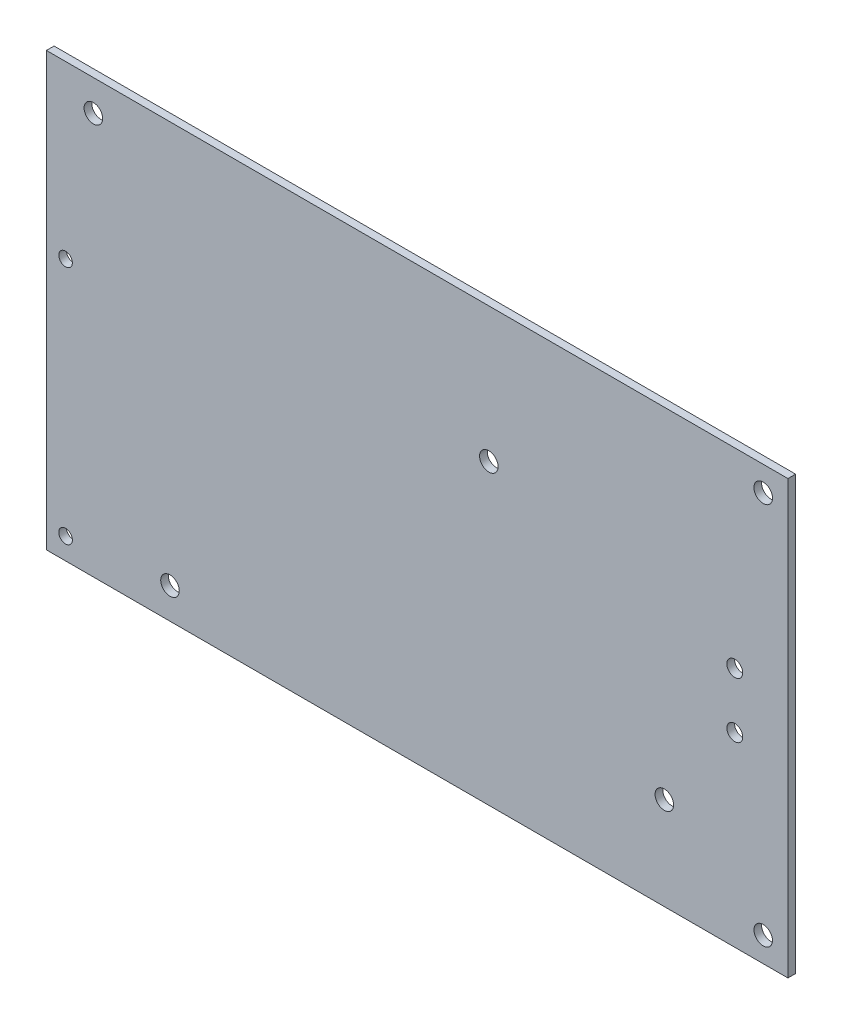
SolidWorks part; units mm, degrees
ref_plane "Front" through (0, 0, 0) normal (0, 0, 1) x (1, 0, 0)
ref_plane "Top" through (0, 0, 0) normal (0, 1, 0) x (1, 0, 0)
ref_plane "Right" through (0, 0, 0) normal (1, 0, 0) x (0, 0, -1)
sketch "Sketch1" plane through (0, 0, 0) normal (0, 0, 1) x (1, 0, 0)
  line L1 (0, 0) -> (152.4, 0)
  line L2 (0, 0) -> (0, -88.9)
  line L3 (0, -88.9) -> (152.4, -88.9)
  line L4 (152.4, 0) -> (152.4, -88.9)
  dimension "D1" = 152.4
  dimension "D2" = 88.9
extrude "Extrude1" add sketch "Sketch1" along normal blind 1.5748
sketch "Sketch2" plane through (0, 0, 1.5748) normal (0, 0, 1) x (1, 0, 0)
  line L0 (0, 0) -> (0, -88.9) construction
  line L1 (0, -88.9) -> (152.4, -88.9) construction
  line L2 (152.4, -88.9) -> (152.4, 0) construction
  line L3 (152.4, 0) -> (0, 0) construction
  circle A0 centre (3.937, -84.4804) radius 1.397
  circle A1 centre (3.937, -35.1536) radius 1.397
  circle A2 centre (147.32, -83.82) radius 1.905
  circle A3 centre (147.32, -5.08) radius 1.905
  dimension "D1" = 2.794
  dimension "D2" = 2.794
  dimension "D7" = 3.81
  dimension "D10" = 3.81
  dimension "D3" = 3.937
  dimension "D4" = 4.4196
  dimension "D5" = 3.937
  dimension "D6" = 49.3268
  dimension "D8" = 5.08
  dimension "D9" = 5.08
  dimension "D11" = 5.08
  dimension "D12" = 5.08
extrude "Cut-Extrude1" cut sketch "Sketch2" against normal blind 1.5748
sketch "Sketch3" plane through (0, 0, 1.5748) normal (0, 0, 1) x (1, 0, 0)
  line L0 (0, -88.9) -> (152.4, -88.9) construction
  line L1 (152.4, -88.9) -> (152.4, 0) construction
  circle A0 centre (141.478, -50.673) radius 1.6256
  circle A1 centre (141.478, -39.243) radius 1.6256
  dimension "D1" = 3.2512
  dimension "D4" = 3.2512
  dimension "D2" = 38.227
  dimension "D3" = 10.922
  dimension "D5" = 11.43
extrude "Cut-Extrude2" cut sketch "Sketch3" against normal blind 10
sketch "Sketch4" plane through (0, 0, 1.5748) normal (0, 0, 1) x (1, 0, 0)
  line L0 (0, -88.9) -> (152.4, -88.9) construction
  line L1 (0, 0) -> (0, -88.9) construction
  line L2 (152.4, 0) -> (0, 0) construction
  line L3 (152.4, -88.9) -> (152.4, 0) construction
  circle A0 centre (25.4, -82.55) radius 1.905
  circle A1 centre (9.652, -6.35) radius 1.905
  circle A2 centre (90.932, -27.686) radius 1.905
  circle A3 centre (127, -69.85) radius 1.905
  dimension "D1" = 3.81
  dimension "D4" = 3.81
  dimension "D7" = 3.81
  dimension "D8" = 3.81
  dimension "D2" = 6.35
  dimension "D3" = 25.4
  dimension "D5" = 6.35
  dimension "D6" = 9.652
  dimension "D9" = 25.4
  dimension "D10" = 19.05
  dimension "D11" = 61.468
  dimension "D12" = 27.686
extrude "Cut-Extrude3" cut sketch "Sketch4" against normal blind 10
